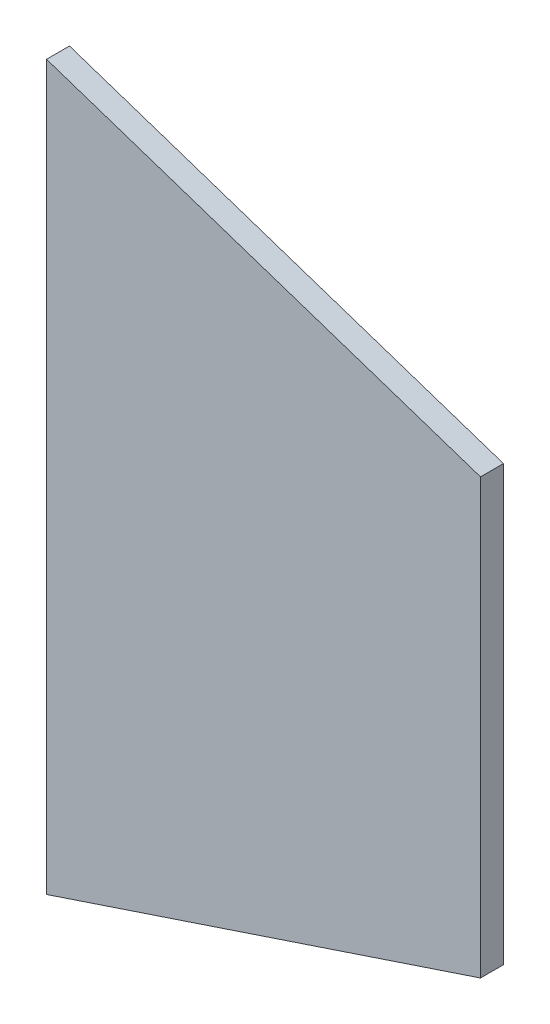
SolidWorks part; units mm, degrees
ref_plane "Front Plane" through (0, 0, 0) normal (0, 0, 1) x (1, 0, 0)
ref_plane "Top Plane" through (0, 0, 0) normal (0, 1, 0) x (1, 0, 0)
ref_plane "Right Plane" through (0, 0, 0) normal (1, 0, 0) x (0, 0, -1)
sketch "Sketch1" plane through (0, 0, 0) normal (0, 0, 1) x (1, 0, 0)
  line L0 (0, 374.2151) -> (0, -368.9959) construction
  line L1 (-577.763, 0) -> (528.7027, 0) construction
  line L2 (95.25, 127) -> (95.25, -127)
  line L3 (95.25, 127) -> (247.65, 76.2)
  line L4 (247.65, 76.2) -> (247.65, -76.2)
  line L5 (95.25, -127) -> (247.65, -76.2)
  point P10 (247.65, 0)
  point P11 (95.25, 0)
  dimension "D1" = 152.4
  dimension "D2" = 76.2
  dimension "D3" = 127
  dimension "D4" = 95.25
extrude "Boss-Extrude1" add sketch "Sketch1" along normal blind 4.0323 and the other way blind 4.0323
